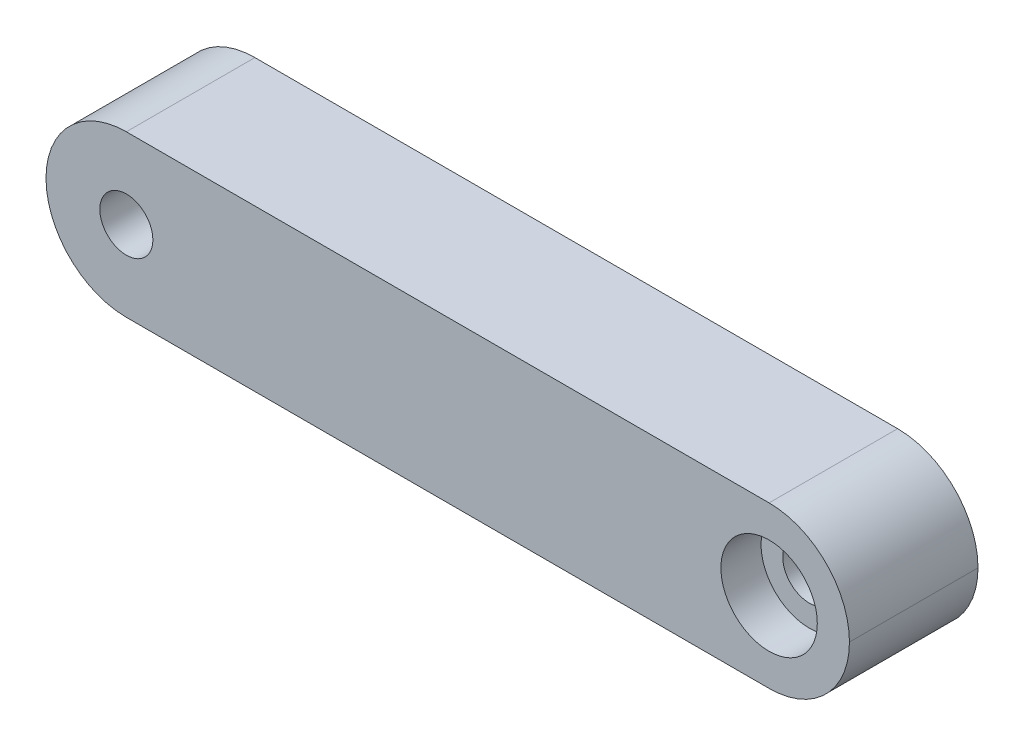
SolidWorks part; units mm, degrees
ref_plane "Přední rovina" through (0, 0, 0) normal (0, 0, 1) x (1, 0, 0)
ref_plane "Horní rovina" through (0, 0, 0) normal (0, 1, 0) x (1, 0, 0)
ref_plane "Pravá rovina" through (0, 0, 0) normal (1, 0, 0) x (0, 0, -1)
sketch "Skica1" plane through (0, 0, 0) normal (0, 0, 1) x (1, 0, 0)
  line L1 (0, 0) -> (50, 0)
  line L2 (0, 0) -> (0, 10)
  line L3 (0, 10) -> (50, 10)
  line L4 (50, 0) -> (50, 10)
  dimension "D1" = 50
  dimension "D2" = 10
extrude "Přidat vysunutím1" add sketch "Skica1" along normal blind 8
sketch "Skica2" plane through (0, 0, 8) normal (0, 0, 1) x (1, 0, 0)
  line L0 (0, 0) -> (50, 0) construction
  line L1 (0, 10) -> (0, 0) construction
  line L2 (50, 0) -> (50, 10) construction
  circle A0 centre (5, 5) radius 1.65
  circle A1 centre (45, 5) radius 1.65
  dimension "D1" = 3.3
  dimension "D2" = 3.3
  dimension "D3" = 5
  dimension "D4" = 5
  dimension "D5" = 5
  dimension "D6" = 5
extrude "Odebrat vysunutím1" cut sketch "Skica2" against normal through all
fillet "Zaoblit2" radius 5 4 edges at (50, 0, 4) (50, 10, 4) (0, 0, 4) (0, 10, 4)
sketch "Skica3" plane through (0, 0, 8) normal (0, 0, 1) x (1, 0, 0)
  circle A1 centre (45, 5) radius 3
  dimension "D1" = 6
extrude "Odebrat vysunutím2" cut sketch "Skica3" against normal blind 2.5
sketch "Skica4" plane through (0, 0, 0) normal (0, 0, -1) x (-1, 0, 0)
  line L0 (-45, 10) -> (-5, 10) construction
  line L1 (-6.5877, 7.75) -> (-8.1754, 5)
  line L2 (-8.1754, 5) -> (-6.5877, 2.25)
  line L3 (-6.5877, 2.25) -> (-3.4123, 2.25)
  line L4 (-3.4123, 2.25) -> (-1.8246, 5)
  line L5 (-1.8246, 5) -> (-3.4123, 7.75)
  line L6 (-3.4123, 7.75) -> (-6.5877, 7.75)
  circle A0 centre (-5, 5) radius 2.75 construction
  dimension "D1" = 5.5
  dimension "D2" = 60
extrude "Odebrat vysunutím3" cut sketch "Skica4" against normal blind 2.5
